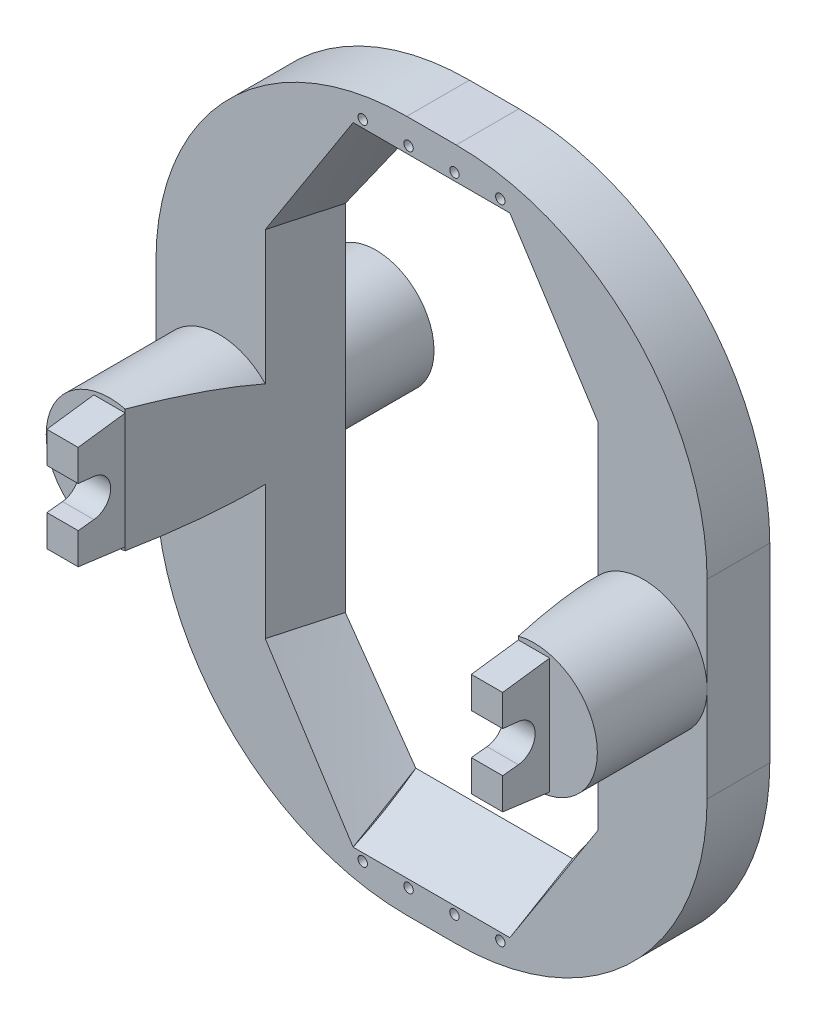
SolidWorks part; units mm, degrees
ref_plane "前视基准面" through (0, 0, 0) normal (0, 0, 1) x (1, 0, 0)
ref_plane "上视基准面" through (0, 0, 0) normal (0, 1, 0) x (1, 0, 0)
ref_plane "右视基准面" through (0, 0, 0) normal (1, 0, 0) x (0, 0, -1)
sketch "草图1" plane through (0, 0, 0) normal (0, 0, 1) x (1, 0, 0)
  circle A0 centre (0, 0) radius 15
  circle A1 centre (0, 0) radius 18.5
  dimension "D1" = 37
  dimension "D2" = 30
extrude "凸台-拉伸1" add sketch "草图1" along normal blind 30
sketch "草图2" plane through (0, 0, 30) normal (0, 0, 1) x (1, 0, 0)
  circle A0 centre (0, 0) radius 20.2
  circle A1 centre (0, 0) radius 15
  circle A2 centre (0, 0) radius 15 construction
  dimension "D1" = 40.4
extrude "凸台-拉伸2" add sketch "草图2" along normal blind 5
sketch "草图3" plane through (0, 0, 35) normal (0, 0, 1) x (1, 0, 0)
  circle A0 centre (0, 0) radius 20.2
extrude "凸台-拉伸3" add sketch "草图3" along normal blind 50
sketch "草图5" plane through (0, 0, 0) normal (1, 0, 0) x (0, -1, 0)
  line L0 (0, -1085) -> (0, 48915) construction
  line L1 (-20.2, -85) -> (20.2, -85) construction
  line L3 (-5.9661, -95) -> (5.9661, -95) construction
  line L4 (-18.5, -85) -> (18.5, -85)
  line L6 (-5.9661, -95) -> (-6.5, -100)
  line L7 (-6.5, -100) -> (-16.5, -100)
  line L8 (-16.5, -100) -> (-18.5, -85)
  line L9 (5.9661, -95) -> (6.5, -100)
  line L10 (6.5, -100) -> (16.5, -100)
  line L11 (16.5, -100) -> (18.5, -85)
  line L12 (-6.5, -100) -> (6.5, -100) construction
  arc A0 (-5.9661, -95) -> (5.9661, -95) centre (0, -95.6371) cw
  point P5 (0, -85)
  point P14 (0, 0)
  point P15 (0, 0)
  point P16 (-7.2176, -113.1062)
  point P17 (0, -97.0663)
  point P18 (-15.4558, -106.4542)
  point P19 (-12.4789, -105.9289)
  point P20 (0, 0)
  point P21 (-20.2, -85)
  point P22 (-15.0124, -105.4289)
  point P23 (-6.8042, -103.9114)
  point P24 (-16.5, -100)
  point P25 (0, 0)
  point P26 (0, 0)
  point P27 (-18.7033, -84.9665)
  dimension "D1" = 6
  dimension "D2" = 10
  dimension "D3" = 15
  dimension "D4" = 13
  dimension "D5" = 10
  dimension "D6" = 37
extrude "凸台-拉伸4" add sketch "草图5" along normal blind 5 and the other way blind 5
sketch "草图6" plane through (0, 0, 30) normal (0, 0, -1) x (-1, 0, 0)
  line L0 (20.2, 0) -> (20.2, 110.3465)
  line L1 (20.2, 110.3465) -> (-155.6, 110.3465)
  line L3 (-155.6, -110.3465) -> (20.2, -110.3465)
  line L4 (20.2, -110.3465) -> (20.2, 0)
  line L5 (-1000, 0) -> (49000, 0) construction
  line L6 (-67.7, -927.1852) -> (-67.7, 49072.8148) construction
  line L7 (-155.6, 110.3465) -> (-155.6, 0)
  line L8 (-155.6, 0) -> (-155.6, -110.3465)
  line L9 (-115.2, 56.5058) -> (-92.7, 56.5058)
  line L11 (-115.2, -56.5058) -> (-115.2, 56.5058)
  line L13 (-20.2, -56.5058) -> (-20.2, 56.5058)
  line L14 (-115.2, -56.5058) -> (-20.2, 56.5058) construction
  line L15 (-115.2, 56.5058) -> (-20.2, -56.5058) construction
  line L16 (-92.7, 56.5058) -> (-92.7, 85)
  line L17 (-92.7, 85) -> (-42.7, 85)
  line L18 (-42.7, 85) -> (-42.7, 56.5058)
  line L19 (-42.7, 56.5058) -> (-20.2, 56.5058)
  line L20 (-115.2, -56.5058) -> (-92.7, -56.5058)
  line L21 (-92.7, -56.5058) -> (-92.7, -85)
  line L22 (-92.7, -85) -> (-42.7, -85)
  line L23 (-42.7, -85) -> (-42.7, -56.5058)
  line L24 (-42.7, -56.5058) -> (-20.2, -56.5058)
  circle A0 centre (0, 0) radius 20.2 construction
  point P11 (0, 0)
  point P13 (-67.7, 110.3465)
  point P17 (-67.7, 0)
  point P28 (0, 0)
  point P29 (0, 0)
  point P30 (-86.9207, -87.9382)
  point P31 (-90.1185, -82.1241)
  point P32 (-88.0836, 53.9257)
  point P33 (20.2, 117.7355)
  point P34 (20.2, -119.3524)
  point P35 (-155.6, -110.3465)
  dimension "D1" = 95
  dimension "D2" = 170
  dimension "D3" = 50
extrude "凸台-拉伸5" add sketch "草图6" against normal blind 20
ref_plane "基准面4" through (67.7, 0, 0) normal (-1, 0, 0) x (0, 0, 1)
mirror "镜向1" about plane through (67.7, 0, 0) normal (-1, 0, 0) of "凸台-拉伸4", "凸台-拉伸3", "凸台-拉伸2"
fillet "圆角1" radius 80 4 edges at (-20.2, 110.3465, 40) (-20.2, -110.3465, 40) (155.6, -110.3465, 40) (155.6, 110.3465, 40)
sketch "草图7" plane through (67.7, 0, 0) normal (1, 0, 0) x (0, 0, -1)
  circle A0 centre (-95.6371, 0) radius 110
  dimension "D1" = 220
sketch "草图10" plane through (67.7, 0, 0) normal (-1, 0, 0) x (0, 0, 1)
  line L0 (95.6371, 0) -> (95.6371, 110.3465)
  line L1 (95.6371, 110.3465) -> (30, 110.3465)
extrude "切除-拉伸2" cut sketch "草图7" against normal up to surface and the other way up to surface up to face at (42.7, 70.7529, 40) other way up to face at (92.7, 70.7529, 40)
sketch "草图11" plane through (0, 0, 30) normal (0, 0, -1) x (-1, 0, 0)
  circle A0 centre (-89.6461, -102.4895) radius 1.5
  circle A1 centre (-75.0154, -102.4895) radius 1.5
  circle A2 centre (-60.3846, -102.4895) radius 1.5
  circle A3 centre (-45.7539, -102.4895) radius 1.5
extrude "切除-拉伸3" cut sketch "草图11" against normal blind 25
ref_plane "基准面6" through (0, 0, 0) normal (0, 1, 0) x (1, 0, 0)
mirror "镜向2" about plane through (0, 0, 0) normal (0, 1, 0) of "切除-拉伸3"
ref_plane "基准面7" through (26.4693, 0, 7.3151) normal (0.9639, 0, 0.2664) x (0.2664, 0, -0.9639)
sketch "草图12" plane through (26.4693, 0, 7.3151) normal (0.9639, 0, 0.2664) x (0.2664, 0, -0.9639)
  line L0 (-80.5969, 56.5058) -> (-80.5969, -56.5058)
  line L1 (-80.5969, -56.5058) -> (-23.5352, -56.5058)
  line L3 (-23.5352, -56.5058) -> (-23.5352, 56.5058)
  line L5 (-23.5352, 56.5058) -> (-80.5969, 56.5058)
  line L6 (-80.5969, -18.5) -> (-80.5969, 18.5) construction
  line L10 (-23.5352, -56.5058) -> (-23.5352, 56.5058) construction
  line L11 (-42.8126, 56.5058) -> (-36.8191, 56.5058) construction
  line L12 (-42.8126, -56.5058) -> (-23.5352, -56.5058) construction
  point P8 (-78.1837, -20.1925)
  point P13 (0, 0)
  point P14 (0, 0)
  point P17 (0, 0)
  point P18 (-37.8153, -24.5156)
  point P19 (0, 0)
  point P21 (0, 0)
extrude "切除-拉伸4" cut sketch "草图12" along normal blind 20
mirror "镜向3" about plane through (67.7, 0, 0) normal (-1, 0, 0) of "切除-拉伸4"
sketch "草图14" plane through (0, 0, 50) normal (0, 0, 1) x (1, 0, 0)
  line L0 (14.6727, 56.5058) -> (42.7, 100.0862)
  line L1 (42.7, 100.0862) -> (92.7, 100.0862)
  line L2 (92.7, 100.0862) -> (120.7273, 56.5058)
  line L3 (120.7273, 56.5058) -> (120.7273, -56.5058)
  line L4 (120.7273, -56.5058) -> (92.7, -100.0862)
  line L5 (92.7, -100.0862) -> (42.7, -100.0862)
  line L6 (42.7, -100.0862) -> (14.6727, -56.5058)
  line L7 (14.6727, -56.5058) -> (14.6727, 56.5058)
sketch "草图15" plane through (0, 0, 30) normal (0, 0, -1) x (-1, 0, 0)
  line L0 (-92.7, 88.271) -> (-115.2, 56.5058)
  line L1 (-115.2, 56.5058) -> (-115.2, -56.5058)
  line L2 (-115.2, -56.5058) -> (-92.7, -88.271)
  line L3 (-92.7, -88.271) -> (-42.7, -88.271)
  line L4 (-42.7, -88.271) -> (-20.2, -56.5058)
  line L5 (-20.2, -56.5058) -> (-20.2, 56.5058)
  line L6 (-20.2, 56.5058) -> (-42.7, 88.271)
  line L7 (-42.7, 88.271) -> (-92.7, 88.271)
loft "切除-放样1" cut profiles "草图14", "草图15" connector at (92.7, 100.0862, 50) connector at (92.7, 88.271, 30)
